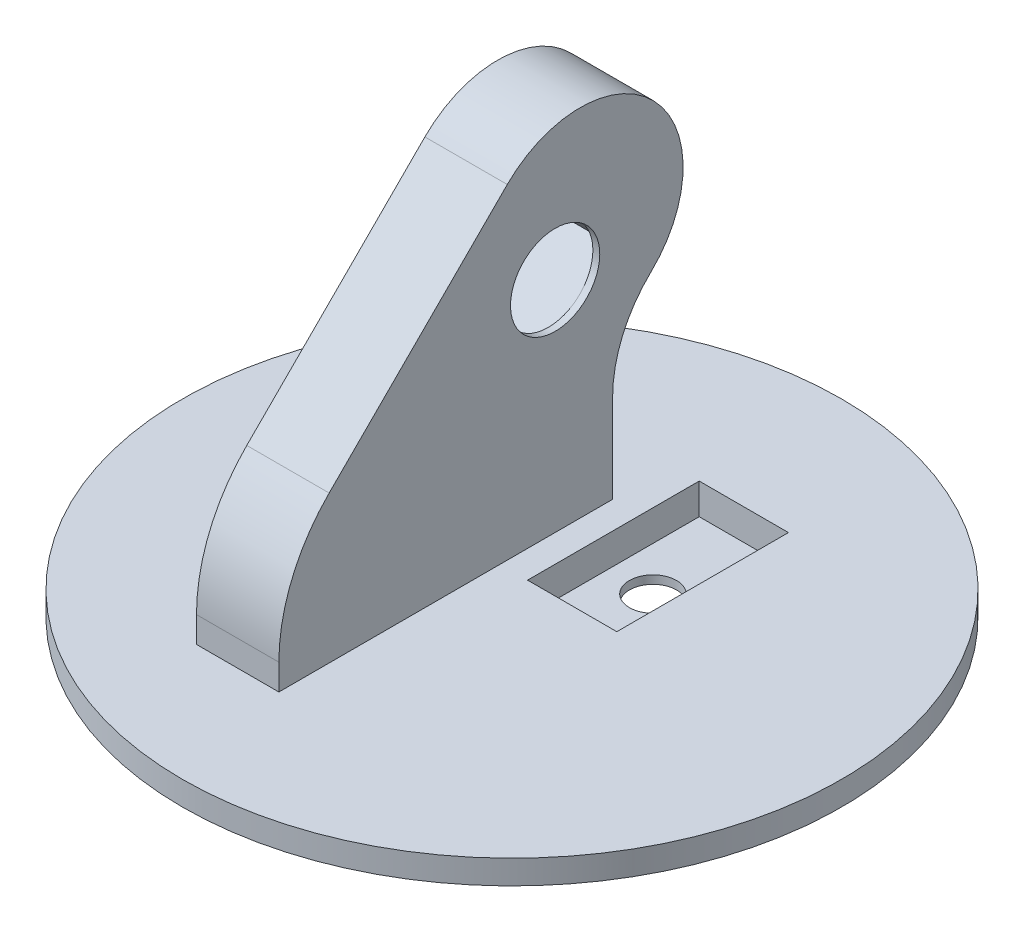
SolidWorks part; units mm, degrees
ref_plane "Front Plane" through (0, 0, 0) normal (0, 0, 1) x (1, 0, 0)
ref_plane "Top Plane" through (0, 0, 0) normal (0, 1, 0) x (1, 0, 0)
ref_plane "Right Plane" through (0, 0, 0) normal (1, 0, 0) x (0, 0, -1)
sketch "Sketch2" plane through (0, 0, 0) normal (0, 1, 0) x (1, 0, 0)
  circle A0 centre (0, 0) radius 48
  dimension "D1" = 96
extrude "Boss-Extrude1" add sketch "Sketch2" along normal blind 3.5
ref_plane "Plane1" through (-4, 0, 0) normal (1, 0, 0) x (0, 0, -1)
sketch "Sketch7" plane through (-4, 0, 0) normal (1, 0, 0) x (0, 0, -1)
  line L0 (18.6521, 16.3561) -> (18.6521, 3.5)
  line L5 (48, 3.5) -> (-48, 3.5) construction
  line L6 (-22.6311, 24.9401) -> (3.3119, 50.8831)
  line L7 (-43.5609, 3.5) -> (18.6521, 3.5)
  line L11 (-29.9535, 3.5) -> (-29.9535, 7.2624)
  arc A4 (24.252, 29.4036) -> (3.3119, 50.8831) centre (13.9185, 40.2765) ccw
  arc A5 (24.252, 29.4036) -> (18.6521, 16.3561) centre (36.6521, 16.3561) ccw
  arc A6 (-22.6311, 24.9401) -> (-29.9535, 7.2624) centre (-4.9535, 7.2624) ccw
  dimension "D1" = 25
  dimension "D4" = 30
  dimension "D3" = 18
  dimension "D5" = 45
extrude "Boss-Extrude2" add sketch "Sketch7" against normal blind 12 contours A5 A4 L6 L7 L0 | A4 | A4 | A4 | L6 A6 L7 region at (-4, 25.827, -1.7732)
ref_plane "Plane2" through (-6, 0, 0) normal (1, 0, 0) x (0, 0, -1)
sketch "Sketch31" plane through (-16, 10.4618, -5.3595) normal (-1, 0, 0) x (0, 0, 1)
  line L0 (-5.4155, 34.0546) -> (11.7496, 18.7458)
  line L1 (11.7496, 18.7458) -> (3.0968, 9.0438)
  line L2 (3.0968, 9.0438) -> (-14.0683, 24.3526)
  line L3 (-14.0683, 24.3526) -> (-5.4155, 34.0546)
  circle A0 centre (-4.9225, 24.9054) radius 6.5
  dimension "D1" = 6.5
extrude "Cut-Extrude18" cut sketch "Sketch31" against normal through all contours A0
extrude "Cut-Extrude19" cut sketch "Sketch31<3>" against normal blind 11 contours L0 L1 L2 L3
sketch "Sketch31<3>" plane through (-16, 10.4618, -5.3595) normal (-1, 0, 0) x (0, 0, 1) same geometry as "Sketch31"
sketch "Sketch32" plane through (-16, 0, 0) normal (-1, 0, 0) x (0, 0, 1)
  line L0 (6.3901, 29.2076) -> (-2.2627, 19.5056) construction
  circle A0 centre (-17.0806, 41.2645) radius 1
  circle A1 centre (3.9294, 22.6926) radius 1
  arc A3 (-14.6084, 40.2182) -> (-15.5944, 39.1126) centre (-10.282, 35.3672) ccw construction
  dimension "D1" = 2.5
  dimension "D2" = 2.5
extrude "Cut-Extrude20" cut sketch "Sketch32" against normal blind 4.5
sketch "Sketch33" plane through (0, 0, 0) normal (0, -1, 0) x (1, 0, 0)
  circle A0 centre (0, 0) radius 43.5
extrude "Boss-Extrude3" add sketch "Sketch33" along normal blind 2.2
sketch "Sketch34" plane through (0, 3.5, 0) normal (0, 1, 0) x (1, 0, 0)
  line L1 (0, 2.2667) -> (13, 2.2667)
  line L2 (0, 2.2667) -> (0, 27.2667)
  line L3 (0, 27.2667) -> (13, 27.2667)
  line L4 (13, 2.2667) -> (13, 27.2667)
  dimension "D1" = 25
  dimension "D2" = 13
extrude "Cut-Extrude21" cut sketch "Sketch34" against normal blind 4.5
sketch "Sketch35" plane through (70.6968, 3.5, -19.0637) normal (0, 1, 0) x (1, 0, 0)
  circle A0 centre (-64.3095, -4.9168) radius 3.43
extrude "Cut-Extrude22" cut sketch "Sketch35" against normal through all
